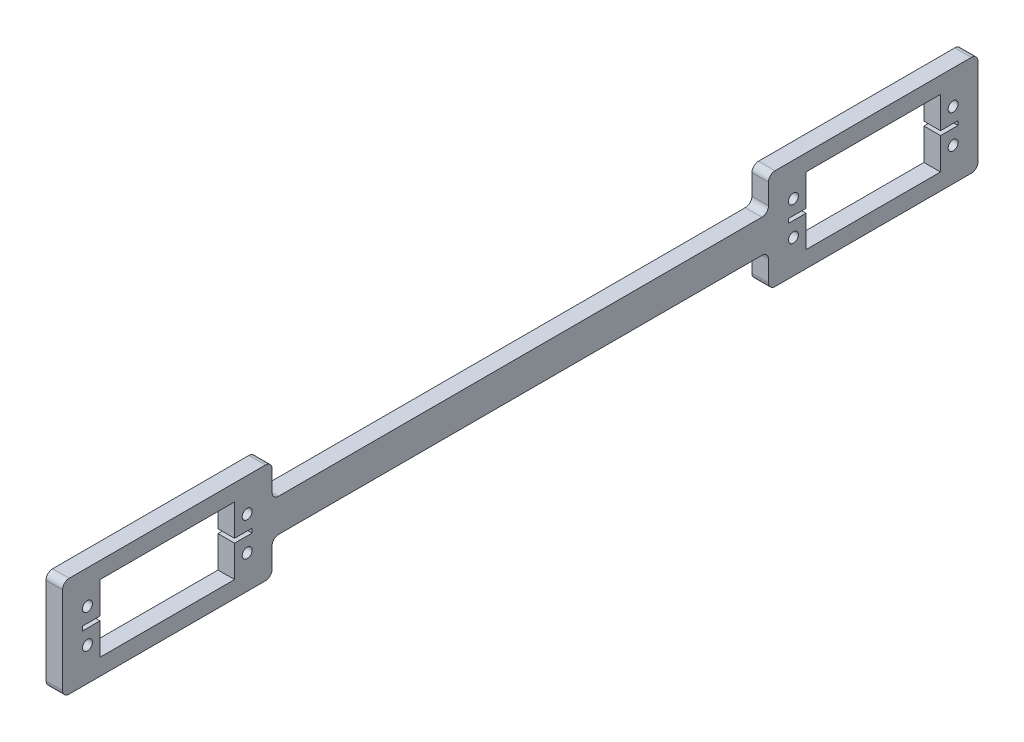
SolidWorks part; units mm, degrees
ref_plane "Front Plane" through (0, 0, 0) normal (0, 0, 1) x (1, 0, 0)
ref_plane "Top Plane" through (0, 0, 0) normal (0, 1, 0) x (1, 0, 0)
ref_plane "Right Plane" through (0, 0, 0) normal (1, 0, 0) x (0, 0, -1)
sketch "Sketch2" plane through (0, 0, 0) normal (1, 0, 0) x (0, 0, -1)
  line L0 (31.65, 5) -> (181.65, 5)
  line L1 (-31.65, 15.16) -> (31.65, 15.16)
  line L2 (-31.65, 15.16) -> (-31.65, -15.16)
  line L3 (-31.65, -15.16) -> (31.65, -15.16)
  line L4 (31.65, 15.16) -> (31.65, -15.16)
  line L5 (-31.65, 15.16) -> (31.65, -15.16) construction
  line L6 (-31.65, -15.16) -> (31.65, 15.16) construction
  line L7 (31.65, 5) -> (31.65, 0)
  line L8 (31.65, 0) -> (31.65, -5)
  line L9 (31.65, -5) -> (181.65, -5)
  line L10 (181.65, -5) -> (181.65, 0)
  line L11 (181.65, 0) -> (181.65, 5)
  line L12 (244.95, -15.16) -> (181.65, 15.16) construction
  line L13 (106.65, 65.8157) -> (106.65, -93.2692) construction
  line L14 (244.95, 15.16) -> (181.65, -15.16) construction
  line L15 (181.65, 0) -> (181.65, -5)
  line L16 (181.65, 5) -> (181.65, 0)
  line L17 (181.65, 15.16) -> (181.65, -15.16)
  line L18 (244.95, -15.16) -> (181.65, -15.16)
  line L19 (244.95, 15.16) -> (244.95, -15.16)
  line L20 (244.95, 15.16) -> (181.65, 15.16)
  point P0 (0, 0)
  point P18 (213.3, 0)
  dimension "D1" = 63.3
  dimension "D2" = 30.32
  dimension "D3" = 150
  dimension "D4" = 10
extrude "Boss-Extrude1" add sketch "Sketch2" along normal blind 5 contours L4 L1 L2 L3 | L10 L11 L0 L4 L9 | L19 L20 L17 L11 L10 L18 region at (0, 0, 0) region at (0, 0, -106.65) region at (0, 0, -213.3)
sketch "Sketch1" plane through (0, 0, 0) normal (1, 0, 0) x (0, 0, -1)
  line L0 (106.65, 65.8157) -> (106.65, -93.2692) construction
  line L1 (-20.32, 10.16) -> (20.32, 10.16)
  line L2 (-20.32, 10.16) -> (-20.32, -10.16)
  line L3 (-20.32, -10.16) -> (20.32, -10.16)
  line L4 (20.32, 10.16) -> (20.32, -10.16)
  line L5 (-20.32, 10.16) -> (20.32, -10.16) construction
  line L6 (-20.32, -10.16) -> (20.32, 10.16) construction
  line L7 (233.62, -10.16) -> (192.98, 10.16) construction
  line L8 (233.62, 10.16) -> (192.98, -10.16) construction
  line L9 (192.98, 10.16) -> (192.98, -10.16)
  line L10 (233.62, -10.16) -> (192.98, -10.16)
  line L11 (233.62, 10.16) -> (233.62, -10.16)
  line L12 (233.62, 10.16) -> (192.98, 10.16)
  line L13 (-31.65, 15.16) -> (31.65, 15.16) construction
  line L14 (-31.65, -15.16) -> (31.65, -15.16) construction
  circle A0 centre (-24.13, 5.08) radius 1.5
  circle A1 centre (-24.13, -5.08) radius 1.5
  circle A2 centre (24.13, 5.08) radius 1.5
  circle A3 centre (24.13, -5.08) radius 1.5
  circle A4 centre (189.17, -5.08) radius 1.5
  circle A5 centre (189.17, 5.08) radius 1.5
  circle A6 centre (237.43, -5.08) radius 1.5
  circle A7 centre (237.43, 5.08) radius 1.5
  point P0 (0, 0)
  point P30 (213.3, 0)
  dimension "D3" = 3
  dimension "D1" = 20.32
  dimension "D2" = 40.64
  dimension "D4" = 3.81
  dimension "D5" = 10.08
  dimension "D6" = 3.81
  dimension "D7" = 10.08
ref_axis "Axis1" through (0, 65.8157, -106.65) along (0, -1, 0)
extrude "Cut-Extrude7" cut sketch "Sketch1" along normal through all
fillet "Fillet1" radius 2 12 edges at (2.5, 15.16, 31.65) (2.5, 15.16, -31.65) (2.5, 5, -31.65) (2.5, -15.16, -31.65) (2.5, -5, -31.65) (2.5, -15.16, 31.65) (2.5, -5, -181.65) (2.5, -15.16, -181.65) (2.5, -15.16, -244.95) (2.5, 15.16, -244.95) (2.5, 5, -181.65) (2.5, 15.16, -181.65)
sketch "Sketch4" plane through (5, 0, 0) normal (1, 0, 0) x (0, 0, -1)
  line L0 (-20.32, -0.635) -> (-25.62, -0.635)
  line L1 (-20.32, 10.16) -> (-20.32, -10.16) construction
  line L2 (-25.62, -0.635) -> (-25.62, 0.635)
  line L3 (-25.62, 0.635) -> (-20.32, 0.635)
  line L4 (-20.32, 0.635) -> (-20.32, -0.635)
  line L5 (-20.32, -0.635) -> (-20.32, 10.16) construction
  line L6 (-20.32, 0.635) -> (-20.32, -10.16) construction
  line L7 (0, 10.16) -> (0, -10.16) construction
  line L8 (20.32, 10.16) -> (-20.32, 10.16) construction
  line L9 (-20.32, -10.16) -> (20.32, -10.16) construction
  line L10 (20.32, 0.635) -> (20.32, -0.635)
  line L11 (20.32, -0.635) -> (25.62, -0.635)
  line L12 (25.62, -0.635) -> (25.62, 0.635)
  line L13 (25.62, 0.635) -> (20.32, 0.635)
  dimension "D1" = 1.27
  dimension "D2" = 5.3
extrude "Cut-Extrude8" cut sketch "Sketch4" against normal through all
sketch "Sketch5" plane through (5, 0, 0) normal (1, 0, 0) x (0, 0, -1)
  line L0 (233.62, -0.635) -> (238.92, -0.635)
  line L1 (233.62, -10.16) -> (233.62, 10.16) construction
  line L2 (238.92, -0.635) -> (238.92, 0.635)
  line L3 (238.92, 0.635) -> (233.62, 0.635)
  line L4 (233.62, 0.635) -> (233.62, -0.635)
  line L5 (233.62, -0.635) -> (233.62, 10.16) construction
  line L6 (233.62, 0.635) -> (233.62, -10.16) construction
  line L7 (213.3, 10.16) -> (213.3, -10.16) construction
  line L8 (233.62, 10.16) -> (192.98, 10.16) construction
  line L9 (192.98, -10.16) -> (233.62, -10.16) construction
  line L10 (192.98, 0.635) -> (192.98, -0.635)
  line L11 (187.68, 0.635) -> (192.98, 0.635)
  line L12 (187.68, -0.635) -> (187.68, 0.635)
  line L13 (192.98, -0.635) -> (187.68, -0.635)
  dimension "D1" = 1.27
  dimension "D2" = 5.3
extrude "Cut-Extrude9" cut sketch "Sketch5" against normal through all
